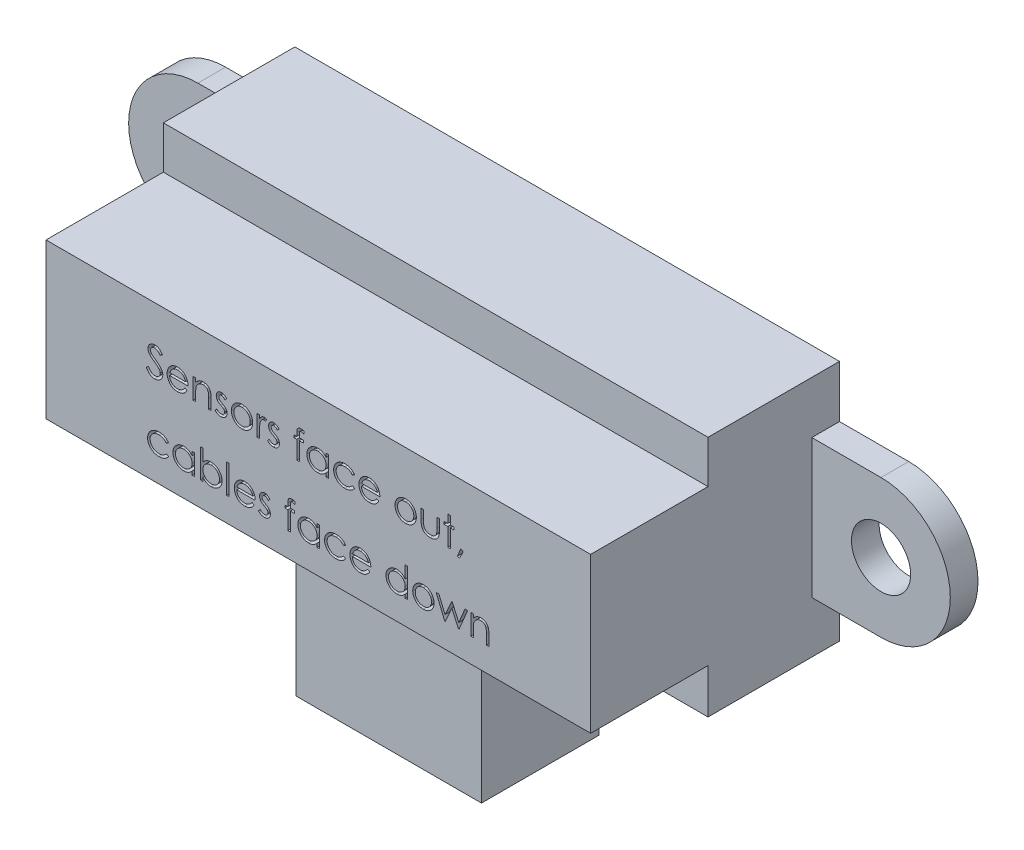
SolidWorks part; units mm, degrees
ref_plane "Front Plane" through (0, 0, 0) normal (0, 0, 1) x (1, 0, 0)
ref_plane "Top Plane" through (0, 0, 0) normal (0, 1, 0) x (1, 0, 0)
ref_plane "Right Plane" through (0, 0, 0) normal (1, 0, 0) x (0, 0, -1)
sketch "Sketch1" plane through (0, 0, 0) normal (0, 0, 1) x (1, 0, 0)
  line L0 (-3.7465, -6.5659) -> (33.2105, -6.5659) construction
  line L1 (0, 0) -> (29.464, 0)
  line L2 (0, 0) -> (0, -2.8194)
  line L3 (0, -13.1064) -> (29.464, -13.1064)
  line L4 (29.464, 0) -> (29.464, -2.8194)
  line L5 (0, 0) -> (29.464, -13.1064) construction
  line L6 (0, -13.1064) -> (29.464, 0) construction
  line L7 (-3.7465, -2.8194) -> (0, -2.8194)
  line L8 (-3.7465, -10.3124) -> (0, -10.3124)
  line L9 (29.464, -2.8194) -> (33.2105, -2.8194)
  line L10 (29.464, -10.3124) -> (33.2105, -10.3124)
  line L11 (0, -10.3124) -> (0, -13.1064)
  line L12 (29.464, -10.3124) -> (29.464, -13.1064)
  arc A0 (-3.7465, -2.8194) -> (-3.7465, -10.3124) centre (-3.7465, -6.5659) ccw
  arc A1 (33.2105, -10.3124) -> (33.2105, -2.8194) centre (33.2105, -6.5659) ccw
  circle A2 centre (-3.7465, -6.5659) radius 1.6002
  circle A3 centre (33.2105, -6.5659) radius 1.6002
  point P4 (14.732, -6.5532)
  point P8 (14.732, -6.5659)
  dimension "D3" = 36.957
  dimension "D6" = 3.2004
  dimension "D7" = 3.2004
  dimension "D1" = 29.464
  dimension "D2" = 13.1064
  dimension "D4" = 7.493
  dimension "D5" = 2.8194
extrude "Boss-Extrude1" add sketch "Sketch1" against normal blind 1.4986
sketch "Sketch2" plane through (0, 0, -1.4986) normal (0, 0, -1) x (-1, 0, 0)
  line L1 (-29.464, 0) -> (0, 0)
  line L2 (-29.464, 0) -> (-29.464, -13.1064)
  line L3 (-29.464, -13.1064) -> (0, -13.1064)
  line L4 (0, 0) -> (0, -13.1064)
  line L5 (-29.464, 0) -> (0, -13.1064) construction
  line L6 (-29.464, -13.1064) -> (0, 0) construction
  point P4 (-14.732, -6.5532)
extrude "Boss-Extrude2" add sketch "Sketch2" against normal blind 7.112
sketch "Sketch3" plane through (0, 0, 5.6134) normal (0, 0, 1) x (1, 0, 0)
  line L0 (0, -13.1064) -> (0, 0) construction
  line L1 (0, -2.3114) -> (29.464, -2.3114)
  line L2 (0, -2.3114) -> (0, -10.6934)
  line L3 (0, -10.6934) -> (29.464, -10.6934)
  line L4 (29.464, -2.3114) -> (29.464, -10.6934)
  line L5 (0, -2.3114) -> (29.464, -10.6934) construction
  line L6 (0, -10.6934) -> (29.464, -2.3114) construction
  line L7 (29.464, 0) -> (29.464, -13.1064) construction
  line L8 (0, 0) -> (29.464, 0) construction
  point P4 (14.732, -6.5024)
  dimension "D1" = 2.3114
  dimension "D2" = 8.382
extrude "Boss-Extrude3" add sketch "Sketch3" along normal blind 6.35
sketch "Sketch6" plane through (0, 0, 11.9634) normal (0, 0, 1) x (1, 0, 0)
  text T0 "Sensors face out,\r\ncables face down" font "Century Gothic" height 1.524
extrude "Cut-Extrude1" cut sketch "Sketch6" against normal blind 1.27
sketch "Sketch7" plane through (0, -10.6934, 0) normal (0, -1, 0) x (1, 0, 0)
  line L0 (0, 11.9634) -> (29.464, 11.9634) construction
  line L1 (9.5758, 8.0264) -> (19.6215, 8.0264)
  line L2 (9.5758, 8.0264) -> (9.5758, 1.6764)
  line L3 (9.5758, 1.6764) -> (19.6215, 1.6764)
  line L4 (19.6215, 8.0264) -> (19.6215, 1.6764)
  line L5 (9.5758, 8.0264) -> (19.6215, 1.6764) construction
  line L6 (9.5758, 1.6764) -> (19.6215, 8.0264) construction
  line L7 (0, -1.4986) -> (0, 5.6134) construction
  point P4 (14.5987, 4.8514)
  dimension "D1" = 3.937
  dimension "D2" = 10.0457
  dimension "D3" = 6.35
  dimension "D4" = 9.5758
extrude "Boss-Extrude4" add sketch "Sketch7" along normal blind 10.16
